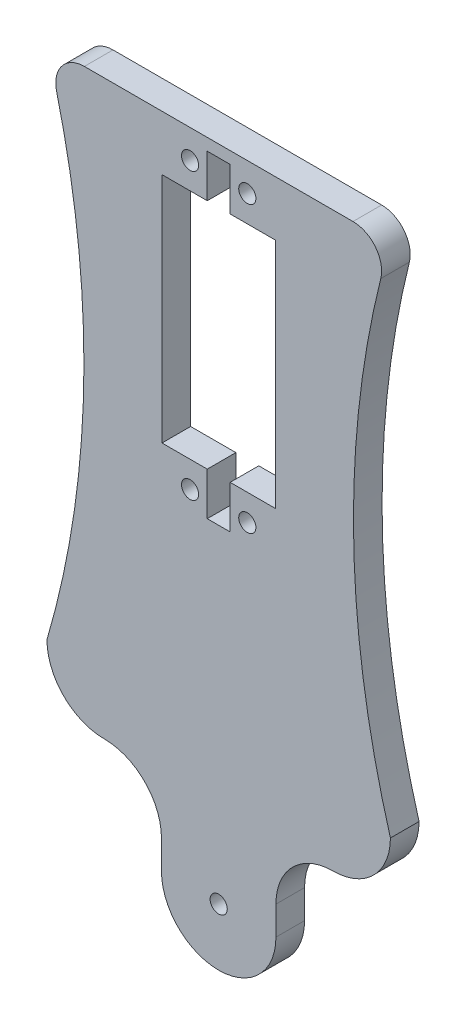
SolidWorks part; units mm, degrees
material "Acrílico (médio-alto impacto)"
ref_plane "Plano frontal" through (0, 0, 0) normal (0, 0, 1) x (1, 0, 0)
ref_plane "Plano superior" through (0, 0, 0) normal (0, 1, 0) x (1, 0, 0)
ref_plane "Plano direito" through (0, 0, 0) normal (1, 0, 0) x (0, 0, -1)
sketch "Esboço1" plane through (0, 0, 0) normal (0, 0, 1) x (1, 0, 0)
  line L0 (-14.0897, 13.1354) -> (-14.0897, 28.1354)
  line L1 (5.9103, 13.1354) -> (5.9103, 28.1354)
  line L2 (5.9103, 28.1354) -> (25.9103, 28.1354)
  line L3 (-34.0897, 128.1354) -> (25.9103, 128.1354)
  line L4 (-34.0897, 128.1354) -> (-34.0897, 28.1354)
  line L5 (-34.0897, 28.1354) -> (-14.0897, 28.1354)
  line L6 (25.9103, 128.1354) -> (25.9103, 28.1354)
  arc A0 (-14.0897, 13.1354) -> (5.9103, 13.1354) centre (-4.0897, 13.1354) ccw
  dimension "D1" = 20
  dimension "D2" = 100
  dimension "D3" = 20
  dimension "D4" = 20
extrude "Ressalto-extrusão1" add sketch "Esboço1" along normal blind 5
sketch "Esboço2" plane through (0, 0, 5) normal (0, 0, 1) x (1, 0, 0)
  circle A0 centre (-4.0897, 13.1354) radius 1.5
  dimension "D1" = 3
extrude "Corte-extrusão1" cut sketch "Esboço2" against normal blind 5
fillet "Filete1" radius 10 4 edges at (5.9103, 28.1354, 2.5) (25.9103, 28.1354, 2.5) (-34.0897, 28.1354, 2.5) (-14.0897, 28.1354, 2.5)
sketch "Esboço3" plane through (0, 0, 5) normal (0, 0, 1) x (1, 0, 0)
  line L0 (-4.0897, 158.1354) -> (-4.0897, 126.1599) construction
  line L2 (-34.0897, 128.1354) -> (-34.0897, 38.1354)
  line L3 (-34.0897, 38.1354) -> (-33.4511, 37.9723)
  line L4 (25.9103, 128.1354) -> (25.9103, 38.1354)
  arc A0 (-34.0897, 38.1354) -> (-34.0897, 128.1354) centre (-187.6312, 83.1354) ccw
  arc A1 (25.9103, 38.1354) -> (25.9103, 128.1354) centre (179.4519, 83.1354) cw
  line M6 (25.9103, 38.1354) -> (25.9103, 128.1354)
  line M8 (-34.0897, 128.1354) -> (-34.0897, 38.1354)
  dimension "D1" = 160
extrude "Corte-extrusão2" cut sketch "Esboço3" against normal blind 5 contours A0 M8 | A1 M6 region at (-31.5018, 83.1354, 5) region at (23.3224, 83.1354, 5)
sketch "Esboço4" plane through (0, 0, 5) normal (0, 0, 1) x (1, 0, 0)
  line L0 (25.9103, 128.1354) -> (-34.0897, 128.1354) construction
  circle A0 centre (-9.0897, 123.1354) radius 1.5
  circle A1 centre (0.9103, 123.1354) radius 1.5
  circle A2 centre (-9.0897, 73.3554) radius 1.5
  circle A3 centre (0.9103, 73.3554) radius 1.5
  dimension "D1" = 49.78
  dimension "D2" = 49.78
  dimension "D3" = 5
  dimension "D4" = 10
  dimension "D5" = 3
  dimension "D6" = 3
  dimension "D7" = 3
  dimension "D8" = 3
  dimension "D9" = 5
  dimension "D10" = 25
  dimension "D11" = 25
  dimension "D12" = 25
extrude "Corte-extrusão3" cut sketch "Esboço4" against normal blind 5
fillet "Filete2" radius 5 2 edges at (25.9103, 128.1354, 2.5) (-34.0897, 128.1354, 2.5)
sketch "Esboço5" plane through (0, 0, 5) normal (0, 0, 1) x (1, 0, 0)
  line L1 (-13.9897, 118.5454) -> (-6.0897, 118.5454)
  line L2 (-13.9897, 118.5454) -> (-13.9897, 77.9454)
  line L3 (-13.9897, 77.9454) -> (-6.0897, 77.9454)
  line L4 (5.8103, 118.5454) -> (5.8103, 77.9454)
  line L6 (-2.0897, 118.5454) -> (-2.0897, 126.0454)
  line L7 (-2.0897, 126.0454) -> (-6.0897, 126.0454)
  line L8 (-6.0897, 118.5454) -> (-6.0897, 126.0454)
  line L9 (-2.0897, 77.9454) -> (5.8103, 77.9454)
  line L10 (-2.0897, 118.5454) -> (5.8103, 118.5454)
  line L11 (-6.0897, 77.9454) -> (-6.0897, 70.4454)
  line L12 (-6.0897, 70.4454) -> (-2.0897, 70.4454)
  line L13 (-2.0897, 77.9454) -> (-2.0897, 70.4454)
  circle A7 centre (-9.0897, 73.3554) radius 1.5 construction
  circle A8 centre (0.9103, 73.3554) radius 1.5 construction
  circle A9 centre (-9.0897, 123.1354) radius 1.5 construction
  circle A10 centre (0.9103, 123.1354) radius 1.5 construction
  dimension "D5" = 4.59
  dimension "D4" = 4.9
  dimension "D1" = 19.8
  dimension "D2" = 40.6
  dimension "D3" = 4.9
  dimension "D6" = 3
  dimension "D7" = 3
  dimension "D8" = 7.5
  dimension "D9" = 3
  dimension "D10" = 3
  dimension "D11" = 7.5
extrude "Corte-extrusão4" cut sketch "Esboço5" against normal blind 5
